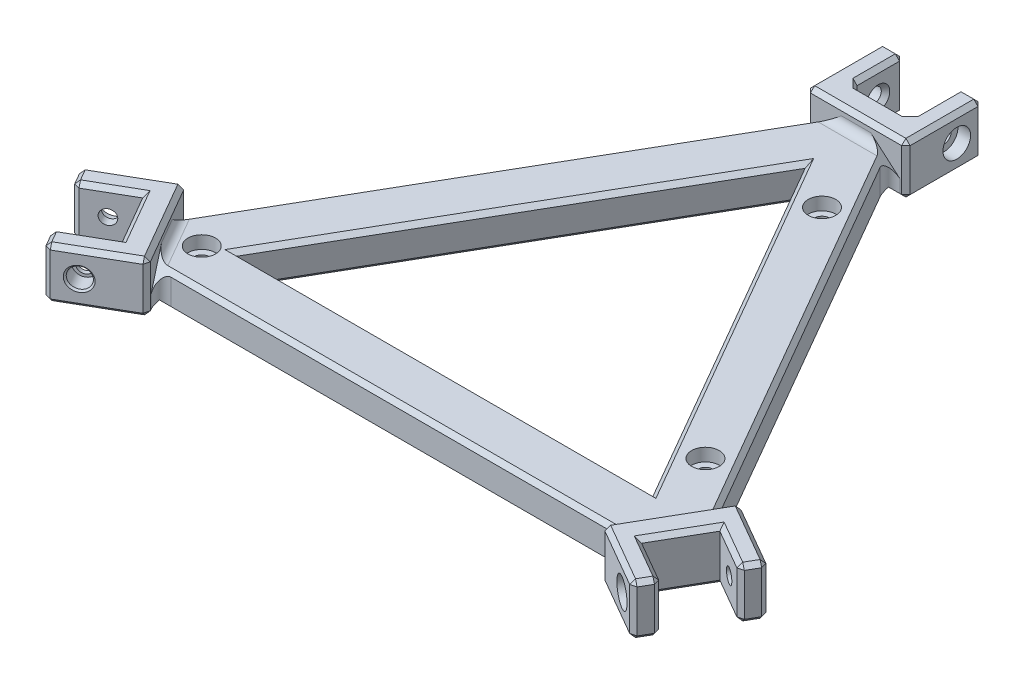
SolidWorks part; units mm, degrees
note: The reader was unsure of these and kept them because the rebuilt part matched: shared geometry of "Sketch1<3>", "Sketch10<4>", "Sketch11<3>", "Sketch12<3>".
ref_plane "Front Plane" through (0, 0, 0) normal (0, 0, 1) x (1, 0, 0)
ref_plane "Top Plane" through (0, 0, 0) normal (0, 1, 0) x (1, 0, 0)
ref_plane "Right Plane" through (0, 0, 0) normal (1, 0, 0) x (0, 0, -1)
sketch "Sketch1" plane through (0, 0, 0) normal (0, 1, 0) x (1, 0, 0)
  line L0 (0, 120.9837) -> (-69.85, 0)
  line L1 (-69.85, 0) -> (69.85, 0)
  line L2 (69.85, 0) -> (0, 120.9837)
  line L3 (0, 120.9837) -> (0, 0) construction
  line L4 (-6.75, 126.9837) -> (-11.75, 126.9837)
  line L5 (-11.75, 126.9837) -> (-11.75, 108.9837)
  line L6 (-11.75, 108.9837) -> (11.75, 108.9837)
  line L7 (11.75, 108.9837) -> (11.75, 126.9837)
  line L8 (11.75, 126.9837) -> (6.75, 126.9837)
  line L9 (6.75, 126.9837) -> (6.75, 114.9837)
  line L10 (6.75, 114.9837) -> (-6.75, 114.9837)
  line L11 (-6.75, 114.9837) -> (-6.75, 126.9837)
  line L12 (78.4212, 2.8457) -> (80.9212, 7.1758)
  line L13 (80.9212, 7.1758) -> (65.3327, 16.1758)
  line L14 (65.3327, 16.1758) -> (53.5827, -4.1758)
  line L15 (53.5827, -4.1758) -> (69.1712, -13.1758)
  line L16 (69.1712, -13.1758) -> (71.6712, -8.8457)
  line L17 (71.6712, -8.8457) -> (61.2788, -2.8457)
  line L18 (61.2788, -2.8457) -> (68.0288, 8.8457)
  line L19 (68.0288, 8.8457) -> (78.4212, 2.8457)
  line L28 (69.85, 0) -> (-34.925, 60.4919) construction
  line L29 (-69.85, 0) -> (34.925, 60.4919) construction
  line L30 (73.225, 5.8457) -> (66.475, -5.8457) construction
  line L31 (-71.6712, -8.8457) -> (-69.1712, -13.1758)
  line L32 (-69.1712, -13.1758) -> (-53.5827, -4.1758)
  line L33 (-53.5827, -4.1758) -> (-65.3327, 16.1758)
  line L34 (-65.3327, 16.1758) -> (-80.9212, 7.1758)
  line L35 (-80.9212, 7.1758) -> (-78.4212, 2.8457)
  line L36 (-78.4212, 2.8457) -> (-68.0288, 8.8457)
  line L37 (-68.0288, 8.8457) -> (-61.2788, -2.8457)
  line L38 (-61.2788, -2.8457) -> (-71.6712, -8.8457)
  line L39 (-66.475, -5.8457) -> (-73.225, 5.8457) construction
  line L40 (0, 96.9837) -> (-49.0654, 12)
  line L41 (-49.0654, 12) -> (49.0654, 12)
  line L42 (49.0654, 12) -> (0, 96.9837)
  point P21 (0, 40.3279)
  point P23 (-59.4577, 6)
  point P29 (-6.75, 120.9837)
  point P30 (0, 114.9837)
  point P31 (69.85, 0)
  point P34 (59.4577, 6)
  dimension "D1" = 139.7
  dimension "D2" = 5
  dimension "D3" = 18
  dimension "D4" = 13.5
  dimension "D5" = 12
  dimension "D6" = 12
extrude "Boss-Extrude1" add sketch "Sketch1" along normal blind 8 contours L33 L1 L14 L2 L6 L0 L42 L41 L40
extrude "Boss-Extrude2" add sketch "Sketch1<3>" along normal blind 12 contours L36 L37 L0 L33 L34 L35 | L0 L37 L1 L33 | L37 L38 L31 L32 L33 L1 | L17 L18 L1 L14 L15 L16 | L1 L18 L2 L14 | L18 L19 L12 L13 L14 L2 | L5 L6 L7 L8 L9 L10 L11 L4
sketch "Sketch1<3>" plane through (0, 0, 0) normal (0, 1, 0) x (1, 0, 0) same geometry as "Sketch1"
hole_wizard "CBORE for M3 SHCS1" positions "Sketch4" profile "Sketch5" counterbore size "M3" standard "ANSI Metric"
sketch "Sketch4" plane through (11.75, 0, 0) normal (1, 0, 0) x (0, 0, -1)
  line L2 (126.9837, 12) -> (126.9837, 0) construction
  line L3 (126.9837, 12) -> (114.9837, 12) construction
  point P0 (120.9837, 6)
  point P10 (126.9837, 6)
  point P13 (120.9837, 12)
sketch "Sketch5" plane through (11.75, 6, -120.9837) normal (0, 1, 0) x (0, 0, -1)
  line L0 (0, 0) -> (0, 5)
  line L1 (0, 5) -> (1.7, 5)
  line L3 (1.7, 5) -> (1.7, 3)
  line L4 (1.7, 3) -> (3.25, 3)
  line L5 (3.25, 3) -> (3.25, 0)
  line L7 (3.25, 0) -> (0, 0)
  line L11 (0, -6.35) -> (0, 107.95) construction
  dimension "Thru Hole Dia." = 3.4
  dimension "Thru Hole Depth" = 5
  dimension "C'Bore Dia." = 6.5
  dimension "C'Bore Depth" = 3
hole_wizard "CBORE for M3 SHCS2" positions "Sketch6" profile "Sketch7" counterbore size "M3" standard "ANSI Metric"
sketch "Sketch6" plane through (11.5875, 0, -20.0701) normal (-0.5, 0, 0.866) x (0.866, 0, 0.5)
  line L0 (66.4919, 12) -> (66.4919, 0) construction
  line L1 (66.4919, 12) -> (54.4919, 12) construction
  point P0 (60.4919, 6)
  point P6 (66.4919, 6)
  point P9 (60.4919, 12)
sketch "Sketch7" plane through (63.975, 6, 10.1758) normal (0, 1, 0) x (0.866, 0, 0.5)
  line L0 (0, 0) -> (0, 5)
  line L1 (0, 5) -> (1.7, 5)
  line L3 (1.7, 5) -> (1.7, 3)
  line L4 (1.7, 3) -> (3.25, 3)
  line L5 (3.25, 3) -> (3.25, 0)
  line L7 (3.25, 0) -> (0, 0)
  line L11 (0, -6.35) -> (0, 107.95) construction
  dimension "Thru Hole Dia." = 3.4
  dimension "Thru Hole Depth" = 5
  dimension "C'Bore Dia." = 6.5
  dimension "C'Bore Depth" = 3
hole_wizard "CBORE for M3 SHCS3" positions "Sketch8" profile "Sketch9" counterbore size "M3" standard "ANSI Metric"
sketch "Sketch8" plane through (-23.3375, 0, -40.4217) normal (-0.5, 0, -0.866) x (-0.866, 0, 0.5)
  line L0 (66.4919, 12) -> (66.4919, 0) construction
  line L1 (66.4919, 12) -> (54.4919, 12) construction
  point P0 (60.4919, 6)
  point P7 (66.4919, 6)
  point P10 (60.4919, 12)
sketch "Sketch9" plane through (-75.725, 6, -10.1758) normal (0, 1, 0) x (-0.866, 0, 0.5)
  line L0 (0, 0) -> (0, 5)
  line L1 (0, 5) -> (1.7, 5)
  line L3 (1.7, 5) -> (1.7, 3)
  line L4 (1.7, 3) -> (3.25, 3)
  line L5 (3.25, 3) -> (3.25, 0)
  line L7 (3.25, 0) -> (0, 0)
  line L11 (0, -6.35) -> (0, 107.95) construction
  dimension "Thru Hole Dia." = 3.4
  dimension "Thru Hole Depth" = 5
  dimension "C'Bore Dia." = 6.5
  dimension "C'Bore Depth" = 3
sketch "Sketch10" plane through (23.3375, 0, -40.4217) normal (0.5, 0, -0.866) x (-0.866, 0, -0.5)
  circle A0 centre (-60.4919, 6) radius 2.35
  circle A1 centre (-60.4919, 6) radius 1.7 construction
  circle A2 centre (-60.4919, 6) radius 1.7
  dimension "D1" = 4.7
extrude "Cut-Extrude1" cut sketch "Sketch10" against normal blind 4 contours A0
extrude "Cut-Extrude6" cut sketch "Sketch10<4>" along direction (0.5, 0, -0.866) on the side against the normal up to next (5 mm away) contours A2
sketch "Sketch10<4>" plane through (23.3375, 0, -40.4217) normal (0.5, 0, -0.866) x (-0.866, 0, -0.5) same geometry as "Sketch10"
sketch "Sketch11" plane through (-11.75, 0, 0) normal (-1, 0, 0) x (0, 0, 1)
  circle A0 centre (-120.9837, 6) radius 2.35
  circle A1 centre (-120.9837, 6) radius 1.7
  circle A2 centre (-120.9837, 6) radius 1.7 construction
  dimension "D1" = 4.7
extrude "Cut-Extrude7" cut sketch "Sketch11" against normal blind 4 contours A0
extrude "Cut-Extrude8" cut sketch "Sketch11<3>" against normal up to next contours A1
sketch "Sketch11<3>" plane through (-11.75, 0, 0) normal (-1, 0, 0) x (0, 0, 1) same geometry as "Sketch11"
sketch "Sketch12" plane through (-11.5875, 0, -20.0701) normal (0.5, 0, 0.866) x (0.866, 0, -0.5)
  circle A0 centre (-60.4919, 6) radius 2.35
  circle A1 centre (-60.4919, 6) radius 1.7
  circle A2 centre (-60.4919, 6) radius 1.7 construction
  dimension "D1" = 4.7
extrude "Cut-Extrude9" cut sketch "Sketch12" against normal blind 4 contours A0
extrude "Cut-Extrude10" cut sketch "Sketch12<3>" against normal up to next contours A1
sketch "Sketch12<3>" plane through (-11.5875, 0, -20.0701) normal (0.5, 0, 0.866) x (0.866, 0, -0.5) same geometry as "Sketch12"
hole_wizard "CBORE for M3 SHCS4" positions "Sketch13" profile "Sketch14" counterbore size "M3" standard "ANSI Metric" end condition up to next
sketch "Sketch13" plane through (0, 8, 0) normal (0, 1, 0) x (1, 0, 0)
  line L0 (0, 96.9837) -> (0, 108.9837) construction
  line L1 (-11.75, 108.9837) -> (11.75, 108.9837) construction
  line L3 (-49.0654, 12) -> (-49.0654, 0) construction
  line L4 (-55.9936, 0) -> (55.9936, 0) construction
  line L6 (49.0654, 12) -> (49.0654, 0) construction
  line L7 (-49.0654, 6) -> (49.0654, 6) construction
  line L8 (-49.0654, 12) -> (-59.4577, 18) construction
  line L9 (-6.9282, 108.9837) -> (-62.9218, 12) construction
  line L10 (0, 96.9837) -> (-10.3923, 102.9837) construction
  line L11 (0, 96.9837) -> (10.3923, 102.9837) construction
  line L12 (62.9218, 12) -> (6.9282, 108.9837) construction
  line L13 (49.0654, 12) -> (59.4577, 18) construction
  line L14 (5.1962, 99.9837) -> (54.2615, 15) construction
  line L15 (-54.2615, 15) -> (-5.1962, 99.9837) construction
  line L16 (-49.0654, 12) -> (-59.4577, 6) construction
  line L17 (-55.9936, 0) -> (-62.9218, 12) construction
  line L19 (49.0654, 12) -> (59.4577, 6) construction
  line L20 (62.9218, 12) -> (55.9936, 0) construction
  line L21 (9.4122, 84.196) -> (12.5181, 95.7871) construction
  line L24 (42.697, 26.5451) -> (54.2881, 23.4393) construction
  line L25 (47.4432, 44.258) -> (39.1219, 13.2028) construction
  line L26 (56.5641, 31.9332) -> (49.4266, 5.2957) construction
  line L27 (-3.9301, 87.7711) -> (27.1251, 79.4499) construction
  line L28 (-5.6255, 100.6487) -> (21.012, 93.5112) construction
  point P0 (10.9651, 89.9916)
  point P2 (-54.2615, 9)
  point P4 (48.4926, 24.9922)
  point P78 (10.9651, 89.9916)
  point P87 (48.4926, 24.9922)
  point P89 (-54.2615, 9)
sketch "Sketch14" plane through (10.9651, 8, -89.9916) normal (1, 0, 0) x (0, 0, 1)
  line L0 (0, 0) -> (0, 8)
  line L1 (0, 8) -> (1.7, 8)
  line L3 (1.7, 8) -> (1.7, 3)
  line L4 (1.7, 3) -> (3.25, 3)
  line L5 (3.25, 3) -> (3.25, 0)
  line L7 (3.25, 0) -> (0, 0)
  line L11 (0, -6.35) -> (0, 107.95) construction
  dimension "Thru Hole Dia." = 3.4
  dimension "Thru Hole Depth" = 8
  dimension "C'Bore Dia." = 6.5
  dimension "C'Bore Depth" = 3
chamfer "Chamfer1" distance 0.4 angle 45 3 edges at (-11.75, 6, -118.6337) (73.6898, 6, -11.3508) (-61.9398, 6, 9.0008)
chamfer "Chamfer2" distance 1 angle 45 84 edges at (0, 0, 0) (0, 8, 0) (-34.925, 8, -60.4919) (-34.925, 0, -60.4919) (34.925, 0, -60.4919) (34.925, 8, -60.4919) (-24.5327, 0, -54.4919) (-24.5327, 8, -54.4919) (0, 0, -12) (0, 8, -12) (24.5327, 0, -54.4919) (24.5327, 8, -54.4919) (6.75, 6, -122.6837) (-6.75, 6, -119.2837) (0, 12, -114.9837) (54.7881, 0, 2.0879) (61.3769, 0, 8.6758) (61.3769, 12, 8.6758) (66.475, 0, 5.8457) (66.475, 12, 5.8457) (64.6538, 0, -3) (64.6538, 12, -3) (73.225, 0, -5.8457) (73.225, 12, -5.8457) (73.1269, 0, -11.6758) (73.1269, 12, -11.6758) (78.4212, 6, -2.8457) (79.6712, 0, -5.0107) (79.6712, 12, -5.0107) (80.9212, 6, -7.1758) (69.1712, 6, 13.1758) (70.4212, 0, 11.0107) (70.4212, 12, 11.0107) (71.6712, 6, 8.8457) (53.5827, 6, 4.1758) (59.4577, 12, -6) (65.3327, 6, -16.1758) (64.1272, 0, -14.0879) (9.3391, 0, -108.9837) (11.75, 0, -117.9837) (11.75, 12, -117.9837) (9.25, 0, -126.9837) (9.25, 12, -126.9837) (0, 0, -114.9837) (-9.25, 0, -126.9837) (-9.25, 12, -126.9837) (-11.75, 0, -117.9837) (-11.75, 12, -117.9837) (-73.1269, 0, -11.6758) (-73.1269, 12, -11.6758) (-73.225, 0, -5.8457) (-73.225, 12, -5.8457) (-64.6538, 0, -3) (-64.6538, 12, -3) (-66.475, 0, 5.8457) (-66.475, 12, 5.8457) (-61.3769, 0, 8.6758) (-61.3769, 12, 8.6758) (-54.7881, 0, 2.0879) (-80.9212, 6, -7.1758) (-79.6712, 0, -5.0107) (-79.6712, 12, -5.0107) (-78.4212, 6, -2.8457) (-71.6712, 6, 8.8457) (-70.4212, 0, 11.0107) (-70.4212, 12, 11.0107) (-69.1712, 6, 13.1758) (-53.5827, 6, 4.1758) (-59.4577, 12, -6) (-65.3327, 6, -16.1758) (-64.1272, 0, -14.0879) (-9.3391, 0, -108.9837) (6.75, 6, -126.9837) (6.75, 0, -120.9837) (6.75, 12, -120.9837) (6.75, 6, -114.9837) (-6.75, 6, -114.9837) (-6.75, 12, -120.9837) (-6.75, 0, -120.9837) (-6.75, 6, -126.9837) (11.75, 6, -126.9837) (11.75, 6, -108.9837) (-11.75, 6, -108.9837) (0, 12, -108.9837)
fillet "Fillet1" radius 2 9 edges at (-62.9218, 4, -12) (-59.4577, 8, -6) (-55.9936, 4, 0) (-6.9282, 4, -108.9837) (6.9282, 4, -108.9837) (0, 8, -108.9837) (62.9218, 4, -12) (55.9936, 4, 0) (59.4577, 8, -6)
